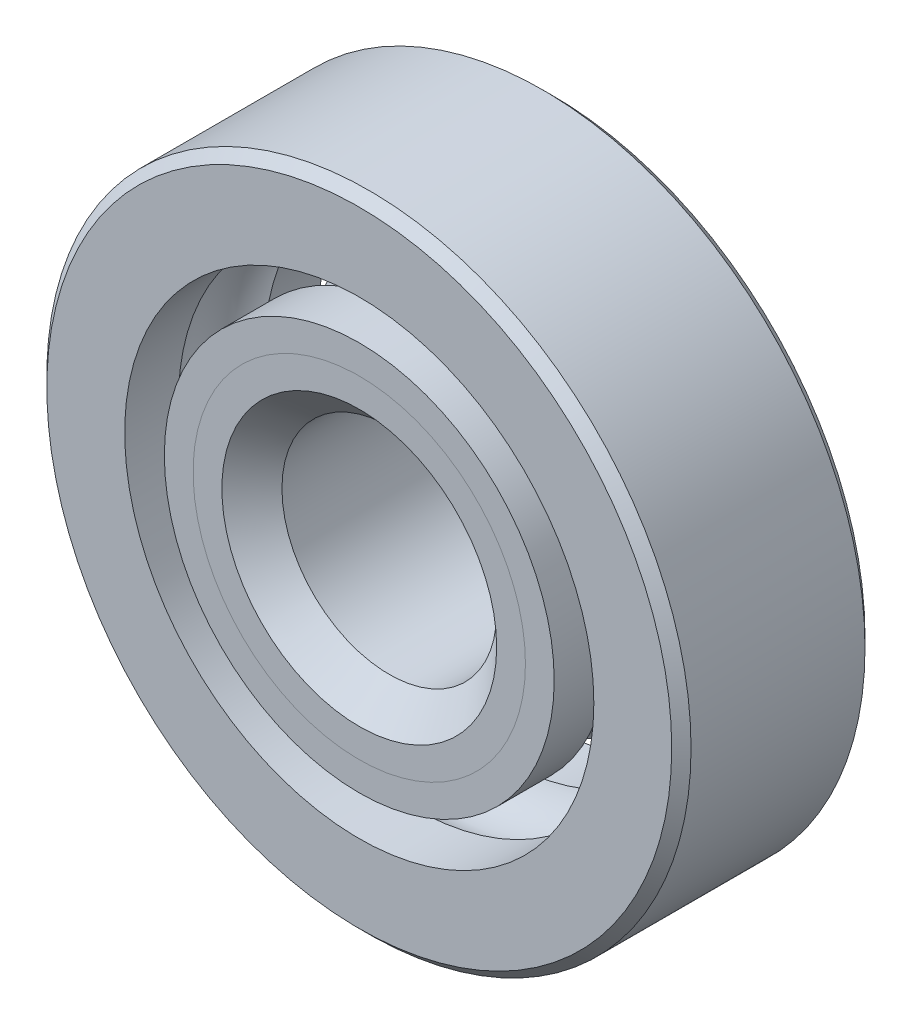
SolidWorks part; units mm, degrees
ref_plane "Front Plane" through (0, 0, 0) normal (0, 0, 1) x (1, 0, 0)
ref_plane "Top Plane" through (0, 0, 0) normal (0, 1, 0) x (1, 0, 0)
ref_plane "Right Plane" through (0, 0, 0) normal (1, 0, 0) x (0, 0, -1)
sketch "Sketch1" plane through (0, 0, 0) normal (1, 0, 0) x (0, 0, -1)
  line L0 (-4.5, 0) -> (4.5, 0) construction
  line L1 (0, 15) -> (0, -15) construction
  line L2 (4.05, 15) -> (-4.05, 15)
  line L3 (-4.05, 15) -> (-4.5, 14.55)
  line L4 (-4.5, 14.55) -> (-4.5, 10.9231)
  line L5 (-4.5, 10.9231) -> (-2, 10.9231)
  line L6 (4.5, 10.9231) -> (2, 10.9231)
  line L7 (4.5, 14.55) -> (4.5, 10.9231)
  line L8 (4.05, 15) -> (4.5, 14.55)
  line L9 (0, 15) -> (0, 10) construction
  line L10 (0, 10) -> (0, 5) construction
  arc A0 (-2, 10.9231) -> (2, 10.9231) centre (0, 10) cw
  point P14 (0, 5)
  dimension "Width" = 9
  dimension "OD" = 30
  dimension "D1" = 45
  dimension "D2" = 0.45
  dimension "D3" = 4
  dimension "D4" = 0.9231
revolve "Revolve1" add sketch "Sketch1" angle 360 about L0
sketch "Sketch2" plane through (0, 0, 0) normal (1, 0, 0) x (0, 0, -1)
  line L0 (-4.5, 9.0769) -> (-2, 9.0769)
  line L1 (-4.5, 14.55) -> (-4.5, -14.55) construction
  line L2 (-4.5, 9.0769) -> (-4.5, 7.7378)
  line L3 (-4.5, 7.7378) -> (-3.1609, 6.3986)
  line L4 (-3.1609, 6.3986) -> (0, 6.3986)
  line L5 (0, 15) -> (0, -15) construction
  line L6 (0, 6.3986) -> (0, 7.7973)
  line L7 (0, 7.7973) -> (0, 5) construction
  line L8 (-4.5, 9.0769) -> (-4.5, 6.3986) construction
  line L9 (-4.5, 6.3986) -> (-3.1609, 6.3986) construction
  arc A0 (-2, 9.0769) -> (0, 7.7973) centre (0, 10) ccw
  arc A1 (2, 10.9231) -> (-2, 10.9231) centre (0, 10) ccw construction
  circle A2 centre (0, 10) radius 2.2027 construction
  dimension "D1" = 45
revolve "Revolve2" add sketch "Sketch2" angle 360 about L0
sketch "Sketch3" plane through (0, 0, 0) normal (1, 0, 0) x (0, 0, -1)
  line L0 (-4.5, 7.7378) -> (-3.1609, 6.3986)
  line L1 (-3.1609, 6.3986) -> (0, 6.3986)
  line L2 (0, 6.3986) -> (0, 7.7973)
  line L3 (-4.5, 7.7378) -> (-4.5, 6.3986)
  line L4 (-4.5, 9.0769) -> (-4.5, 6.3986) construction
  line L5 (-4.5, 6.3986) -> (-3.1014, 5)
  line L6 (-3.1014, 5) -> (4.05, 5)
  line L7 (4.05, 15) -> (4.05, -15) construction
  line L8 (4.05, 5) -> (4.5, 5.45)
  line L9 (4.5, -14.55) -> (4.5, 14.55) construction
  line L10 (4.5, 5.45) -> (4.5, 9.0769)
  line L11 (4.5, 9.0769) -> (2, 9.0769)
  line L13 (4.05, 15) -> (4.5, 14.55) construction
  circle A0 centre (0, 10) radius 2.2027 construction
  arc A1 (2, 9.0769) -> (0, 7.7973) centre (0, 10) cw
revolve "Revolve3" add sketch "Sketch3" angle 360 about L0
sketch "Sketch4" plane through (0, 0, 0) normal (1, 0, 0) x (0, 0, -1)
  line L0 (-2.2027, 10) -> (2.2027, 10)
  circle A1 centre (0, 10) radius 2.2027 construction
  arc A2 (-2.2027, 10) -> (2.2027, 10) centre (0, 10) cw
  arc A3 (2, 10.9231) -> (-2, 10.9231) centre (0, 10) ccw construction
revolve "Revolve4" add sketch "Sketch4" angle 360 about L0
ref_axis "Axis1" through (0, 0, -4.5) along (0, 0, 1)
pattern_circular "CirPattern1" [suppressed] count 10 every 36 about axis through (0, 0, -4.5) along (0, 0, 1) of bodies 104
equation "\"D2@Sketch1\" = \"Width@Sketch1\"*.05"
equation "\"D3@Sketch1\" = \"Width@Sketch1\"/2.25"
equation "\"D4@Sketch1\" = (((\"OD@Sketch1\"-\"Width@Sketch1\")/2)/3.25)/3.5"
equation "\"D2@CirPattern1\" = 360/\"Balls@CirPattern1\""
